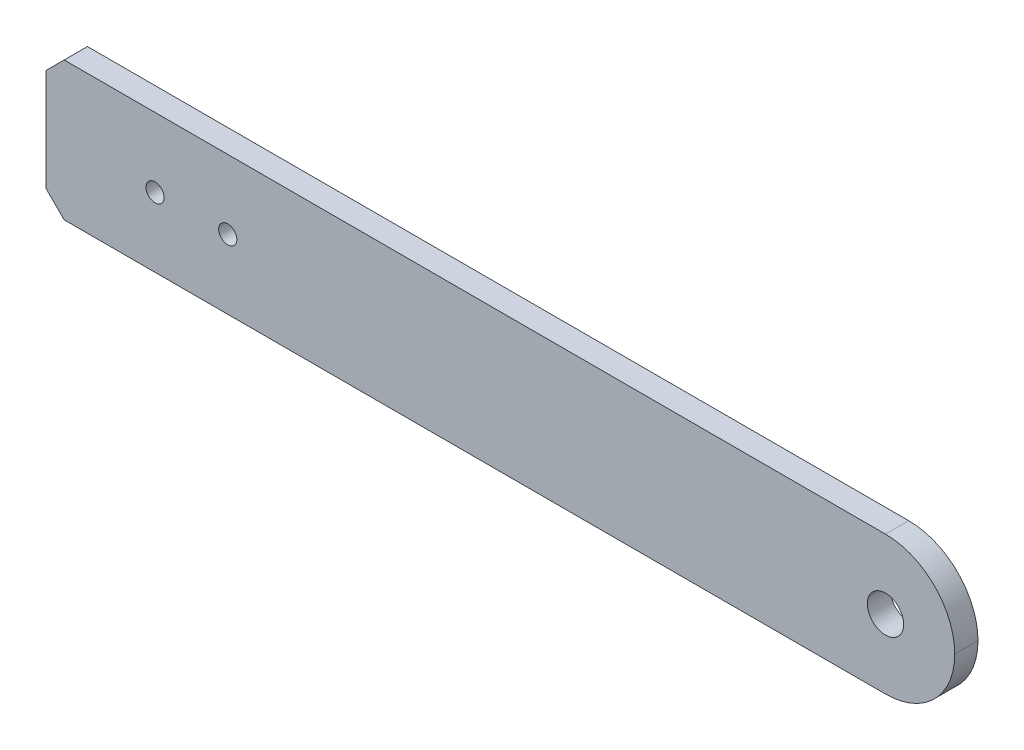
SolidWorks part; units mm, degrees
material "7075-T6, Plate (SS)"
ref_plane "Front Plane" through (0, 0, 0) normal (0, 0, 1) x (1, 0, 0)
ref_plane "Top Plane" through (0, 0, 0) normal (0, 1, 0) x (1, 0, 0)
ref_plane "Right Plane" through (0, 0, 0) normal (1, 0, 0) x (0, 0, -1)
sketch "Sketch1" plane through (0, 0, 0) normal (0, 0, 1) x (1, 0, 0)
  line L1 (-120, 19.05) -> (125, 19.05)
  line L2 (-125, 14.05) -> (-125, -14.05)
  line L3 (-120, -19.05) -> (125, -19.05)
  line L4 (125, 19.05) -> (125, -19.05)
  line L5 (-125, 19.05) -> (125, -19.05) construction
  line L6 (-125, -19.05) -> (125, 19.05) construction
  line L8 (-125, 14.05) -> (-120, 19.05)
  line L9 (-125, -14.05) -> (-120, -19.05)
  point P0 (0, 0)
  dimension "D1" = 38.1
  dimension "D2" = 250
extrude "Boss-Extrude1" add sketch "Sketch1" along normal blind 6.4
hole_wizard "Ø5.0mm Dowel Hole1" positions "Sketch7" profile "Sketch8" hole size "Ø5.0" standard "ISO" end condition through all
sketch "Sketch7" plane through (0, 0, 6.4) normal (0, 0, 1) x (1, 0, 0)
  line L0 (0, 0) -> (125, 0) construction
  line L1 (125, -19.05) -> (125, 19.05) construction
  point P0 (-75, 0)
  point P12 (-95, 0)
  dimension "D1" = 200
  dimension "D2" = 20
sketch "Sketch8" plane through (-75, 0, 6.4) normal (1, 0, 0) x (0, -1, 0)
  line L0 (0, 0) -> (0, 6.4)
  line L1 (0, 6.4) -> (2.5, 6.4)
  line L2 (2.5, 6.4) -> (2.5, 0)
  line L5 (2.5, 0) -> (0, 0)
  line L11 (0, -6.35) -> (0, 107.95) construction
  dimension "Thru Hole Dia." = 5
  dimension "Thru Hole Depth" = 6.4
fillet "Fillet1" radius 19.05 2 edges at (125, -19.05, 3.2) (125, 19.05, 3.2)
sketch "Sketch9" plane through (0, 0, 6.4) normal (0, 0, 1) x (1, 0, 0)
  circle A0 centre (105.95, 0) radius 5
  dimension "D1" = 10
extrude "Cut-Extrude1" cut sketch "Sketch9" against normal up to next
